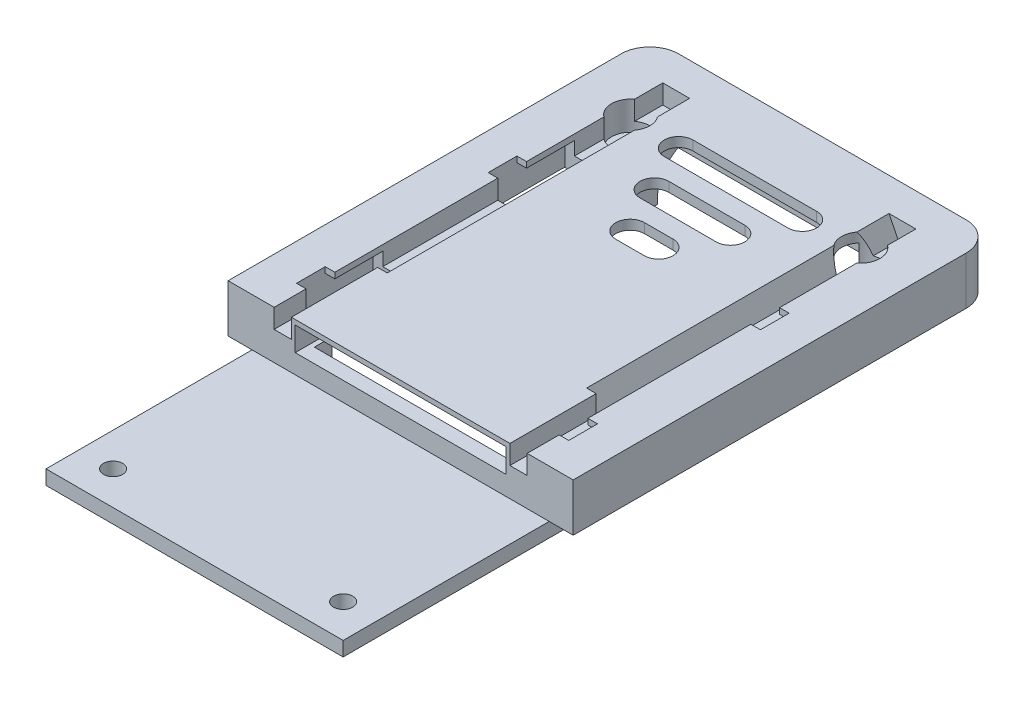
SolidWorks part; units mm, degrees
ref_plane "前视基准面" through (0, 0, 0) normal (0, 0, 1) x (1, 0, 0)
ref_plane "上视基准面" through (0, 0, 0) normal (0, 1, 0) x (1, 0, 0)
ref_plane "右视基准面" through (0, 0, 0) normal (1, 0, 0) x (0, 0, -1)
sketch "草图1" plane through (0, 0, 0) normal (0, 1, 0) x (1, 0, 0)
  line L0 (18, -21) -> (-18, 21) construction
  line L1 (-18, 21) -> (18, 21)
  line L2 (-18, 21) -> (-18, -21)
  line L3 (-18, -21) -> (18, -21)
  line L4 (18, 21) -> (18, -21)
  line L5 (18, 21) -> (-18, -21) construction
  point P4 (0, 0)
  dimension "D1" = 36
  dimension "D2" = 42
extrude "凸台-拉伸1" add sketch "草图1" along normal blind 5
sketch "草图2" plane through (0, 5, 0) normal (0, 1, 0) x (1, 0, 0)
  line L0 (-18, -21) -> (18, -21) construction
  line L1 (-13.2, -21) -> (-11.4, -21)
  line L2 (-13.2, -21) -> (-13.2, 19.55)
  line L3 (-13.2, 19.55) -> (-11.4, 19.55)
  line L4 (-11.4, -21) -> (-11.4, 19.55)
  line L5 (-18, 21) -> (-18, -21) construction
  line L6 (18, 21) -> (-18, 21) construction
  line L7 (0, -21) -> (0, 21) construction
  line L8 (11.4, -21) -> (11.4, 19.55)
  line L9 (13.2, 19.55) -> (11.4, 19.55)
  line L10 (13.2, -21) -> (13.2, 19.55)
  line L11 (13.2, -21) -> (11.4, -21)
  dimension "D1" = 1.8
  dimension "D2" = 4.8
  dimension "D3" = 1.45
extrude "切除-拉伸1" cut sketch "草图2" against normal blind 2
sketch "草图3" plane through (0, 5, 0) normal (0, 1, 0) x (1, 0, 0)
  line L0 (-11.4, -21) -> (11.4, -21) construction
  line L1 (-10.5944, -21) -> (10.4056, -21)
  line L2 (-10.5944, -21) -> (-10.5944, -12.5)
  line L3 (-10.5944, -12.5) -> (10.4056, -12.5)
  line L4 (10.4056, -21) -> (10.4056, -12.5)
  dimension "D1" = 21
  dimension "D2" = 8.5
sketch "草图4" plane through (0, 5, 0) normal (0, 1, 0) x (1, 0, 0)
  line L0 (13.2, -21) -> (13.2, 19.55) construction
  line L1 (13.2, -17.6667) -> (14.2, -17.6667)
  line L2 (13.2, -17.6667) -> (13.2, -14.6667)
  line L3 (13.2, -14.6667) -> (14.2, -14.6667)
  line L4 (14.2, -17.6667) -> (14.2, -14.6667)
  line L5 (13.2, -21) -> (18, -21) construction
  line L6 (13.2, -21) -> (13.2, 19.55) construction
  line L7 (13.2, 2.3333) -> (14.2, 2.3333)
  line L8 (13.2, 2.3333) -> (13.2, 5.3333)
  line L9 (13.2, 5.3333) -> (14.2, 5.3333)
  line L10 (14.2, 2.3333) -> (14.2, 5.3333)
  line L11 (-13.2, 19.55) -> (-13.2, -21) construction
  line L22 (-13.2, -17.6667) -> (-14.2017, -17.6667)
  line L23 (-13.2, -17.6667) -> (-13.2, -14.6667)
  line L24 (-13.2, -14.6667) -> (-14.2017, -14.6667)
  line L25 (-14.2017, -17.6667) -> (-14.2017, -14.6667)
  line L26 (-13.2, 19.55) -> (-13.2, -21) construction
  line L27 (-13.2, 2.3333) -> (-14.2017, 2.3333)
  line L28 (-13.2, 2.3333) -> (-13.2, 5.3333)
  line L29 (-13.2, 5.3333) -> (-14.2017, 5.3333)
  line L30 (-14.2017, 2.3333) -> (-14.2017, 5.3333)
  line L31 (-18, -21) -> (-13.2, -21) construction
  point P26 (-13.7008, 2.3333)
  dimension "D1" = 3
  dimension "D2" = 3.3333
  dimension "D3" = 1
  dimension "D4" = 17
  dimension "D5" = 3
  dimension "D6" = 1
  dimension "D7" = 3
  dimension "D8" = 1.0017
  dimension "D9" = 17
  dimension "D10" = 3
  dimension "D11" = 1.0017
  dimension "D12" = 3.3333
extrude "切除-拉伸2" cut sketch "草图4" against normal through all
sketch "草图5" plane through (0, 0, 0) normal (0, -1, 0) x (1, 0, 0)
  line L1 (-14.2017, 17.6667) -> (-12.4, 17.6667)
  line L2 (-14.2017, 17.6667) -> (-14.2017, 9.6667)
  line L3 (-14.2017, 9.6667) -> (-12.4, 9.6667)
  line L4 (-12.4, 17.6667) -> (-12.4, 9.6667)
  line L5 (-18, -21) -> (-18, 21) construction
  line L6 (18, 21) -> (18, -21) construction
  line L7 (14.2, 17.6667) -> (12.4, 17.6667)
  line L8 (14.2, 17.6667) -> (14.2, 9.6667)
  line L9 (14.2, 9.6667) -> (12.4, 9.6667)
  line L10 (12.4, 17.6667) -> (12.4, 9.6667)
  line L11 (-14.2017, -2.3333) -> (-12.4, -2.3333)
  line L12 (-14.2017, -2.3333) -> (-14.2017, -10.3333)
  line L13 (-14.2017, -10.3333) -> (-12.4, -10.3333)
  line L14 (-12.4, -2.3333) -> (-12.4, -10.3333)
  line L15 (14.2, -2.3333) -> (12.4, -2.3333)
  line L16 (14.2, -2.3333) -> (14.2, -10.3333)
  line L17 (14.2, -10.3333) -> (12.4, -10.3333)
  line L18 (12.4, -2.3333) -> (12.4, -10.3333)
  dimension "D1" = 8
  dimension "D2" = 5.6
  dimension "D3" = 8
  dimension "D4" = 5.6
  dimension "D5" = 5.6
  dimension "D6" = 8
  dimension "D7" = 8
  dimension "D8" = 5.6
extrude "切除-拉伸3" cut sketch "草图5" against normal blind 4.4
ref_plane "基准面5" through (0, 0, 12) normal (0, 0, 1) x (1, 0, 0)
sketch "草图9" plane through (0, 0, 12) normal (0, 0, 1) x (1, 0, 0)
  line L0 (-11.4, 5) -> (-10.4, 5)
  line L1 (-10.5944, 5) -> (10.4056, 5) construction
  line L2 (-10.4, 5) -> (-11.4, 3)
  line L3 (-11.4, 3) -> (-11.4, 5)
  line L4 (11.4, 5) -> (11.4, 3)
  line L5 (11.4, 3) -> (10.4, 5)
  line L6 (10.4, 5) -> (11.4, 5)
  dimension "D1" = 1
  dimension "D2" = 1
extrude "切除-拉伸4" cut sketch "草图9" against normal up to surface (31.55 mm away) up to face at (-12.3, 4, -19.55)
sketch "草图11" plane through (0, 0, 21) normal (0, 0, 1) x (1, 0, 0)
  line L1 (-11, 4.5) -> (11, 4.5)
  line L2 (-11, 4.5) -> (-11, 2)
  line L3 (-11, 2) -> (11, 2)
  line L4 (11, 4.5) -> (11, 2)
  line L5 (0, 2) -> (0, 0) construction
  line L7 (-10.5944, 5) -> (10.4056, 5) construction
  dimension "D1" = 0.5
  dimension "D2" = 2.5
  dimension "D3" = 22
extrude "切除-拉伸5" cut sketch "草图11" against normal blind 8.6
sketch "草图12" plane through (0, 5, 0) normal (0, 1, 0) x (1, 0, 0)
  line L0 (-6.4662, 14.4686) -> (6.4369, 14.4686) construction
  line L1 (-6.4662, 15.9686) -> (6.4369, 15.9686)
  line L2 (-6.4662, 12.9686) -> (6.4369, 12.9686)
  line L3 (-3.9955, 9.4686) -> (3.9437, 9.4686) construction
  line L4 (-3.9955, 10.9686) -> (3.9437, 10.9686)
  line L5 (-3.9955, 7.9686) -> (3.9437, 7.9686)
  line L6 (-1.5248, 4.4686) -> (1.4505, 4.4686) construction
  line L7 (-1.5248, 5.9686) -> (1.4505, 5.9686)
  line L8 (-1.5248, 2.9686) -> (1.4505, 2.9686)
  line L9 (0, 21) -> (-0.0944, -21) construction
  line L10 (18, 21) -> (-18, 21) construction
  line L11 (-10.5944, -21) -> (10.4056, -21) construction
  line L12 (-1.5248, 4.4686) -> (-6.4662, 14.4686) construction
  arc A0 (-6.4662, 15.9686) -> (-6.4662, 12.9686) centre (-6.4662, 14.4686) ccw
  arc A1 (6.4369, 12.9686) -> (6.4369, 15.9686) centre (6.4369, 14.4686) ccw
  arc A2 (-3.9955, 10.9686) -> (-3.9955, 7.9686) centre (-3.9955, 9.4686) ccw
  arc A3 (3.9437, 7.9686) -> (3.9437, 10.9686) centre (3.9437, 9.4686) ccw
  arc A4 (-1.5248, 5.9686) -> (-1.5248, 2.9686) centre (-1.5248, 4.4686) ccw
  arc A5 (1.4505, 2.9686) -> (1.4505, 5.9686) centre (1.4505, 4.4686) ccw
  point P2 (-0.0147, 14.4686)
  point P9 (-0.0259, 9.4686)
  point P16 (-0.0371, 4.4686)
  dimension "D1" = 2
  dimension "D2" = 2
  dimension "D3" = 3
  dimension "D4" = 3
  dimension "D5" = 3
extrude "切除-拉伸6" cut sketch "草图12" against normal up to surface (5 mm away) up to face at (13.3, 0, -6.3333)
sketch "草图13" plane through (0, 0, 0) normal (0, -1, 0) x (1, 0, 0)
  line L5 (-10.5944, 21) -> (10.4056, 21) construction
  line L6 (-16.5, -19.5) -> (16.5, -19.5)
  line L8 (-16.5, -19.5) -> (-16.5, 19.5)
  line L9 (-16.5, 19.5) -> (16.5, 19.5)
  line L10 (16.5, -19.5) -> (16.5, 19.5)
  line L11 (18, 21) -> (18, -21) construction
  line L12 (-18, -21) -> (-18, 21) construction
  line L13 (18, -21) -> (-18, -21) construction
  point P0 (0, 0)
  dimension "D1" = 1.5
  dimension "D2" = 1.5
  dimension "D3" = 1.5
  dimension "D4" = 1.5
extrude "切除-拉伸7" cut sketch "草图13" against normal blind 1.5
sketch "草图14" plane through (0, 1.5, 0) normal (0, -1, 0) x (1, 0, 0)
  line L0 (-16.5, -19.5) -> (16.5, -19.5) construction
  line L1 (-10.5, -19.5) -> (10.5, -19.5)
  line L2 (-10.5, -19.5) -> (-10.5, 19.5)
  line L3 (-10.5, 19.5) -> (10.5, 19.5)
  line L4 (10.5, -19.5) -> (10.5, 19.5)
  line L5 (16.5, 19.5) -> (-16.5, 19.5) construction
  line L8 (0, 19.5) -> (0, -19.5) construction
  dimension "D2" = 21
extrude "切除-拉伸8" cut sketch "草图14" against normal blind 2.5
sketch "草图15" plane through (0, 0, 0) normal (0, -1, 0) x (1, 0, 0)
  line L7 (-10.5, 17.6667) -> (-10.5, 19.5)
  line L8 (18, -21) -> (-18, -21) construction
  line L9 (-15.5, 17.6667) -> (15.5, 17.6667)
  line L10 (-15.5, 17.6667) -> (-15.5, 42.5)
  line L11 (-15.5, 42.5) -> (15.5, 42.5)
  line L12 (15.5, 17.6667) -> (15.5, 42.5)
  line L13 (16.5, 19.5) -> (-16.5, 19.5) construction
  line L14 (-10.5, 19.5) -> (10.5, 19.5)
  line L15 (10.5, 19.5) -> (10.5, 17.6667)
  line L16 (10.5, -19.5) -> (10.5, 19.5) construction
  line L17 (-10.5, 19.5) -> (-10.5, -19.5) construction
  line L19 (0, 42.5) -> (0, 0) construction
  line L21 (-12.4, 17.6667) -> (-14.2017, 17.6667) construction
  line M11 (-16.5, 19.5) -> (16.5, 19.5)
  line M28 (18, 21) -> (-18, 21)
  dimension "D1" = 63.5
  dimension "D2" = 31
extrude "凸台-拉伸2" add sketch "草图15" along normal blind 1.5 separate body contours L19 L11 L10 M28 | L11 L19 L12 M28 | L19 L14 L12 M28 M11 | L19 L10 M28 M11 | L10 L9 L7 M11 | L15 L9 L12 M11 region at (-13, 0, 18.5834) region at (-7.75, 0, 20.25) region at (7.75, 0, 20.25) region at (13, 0, 18.5834) region at (-7.75, 0, 31.75) region at (7.75, 0, 31.75)
sketch "草图16" plane through (0, 1.5, 0) normal (0, -1, 0) x (1, 0, 0)
  line L0 (10.5, 19.5) -> (10.5, 17.6667) construction
  line L1 (-16.5, 17.6667) -> (-10.5, 17.6667)
  line L2 (-16.5, 17.6667) -> (-16.5, 19.5)
  line L3 (-16.5, 19.5) -> (-10.5, 19.5)
  line L4 (-10.5, 17.6667) -> (-10.5, 19.5)
  line L5 (10.5, 17.6667) -> (16.5, 17.6667)
  line L6 (10.5, 17.6667) -> (10.5, 19.5)
  line L7 (10.5, 19.5) -> (16.5, 19.5)
  line L8 (16.5, 17.6667) -> (16.5, 19.5)
  line L9 (-16.5, 19.5) -> (-16.5, -19.5) construction
  line L10 (-10.5, 17.6667) -> (-10.5, 19.5) construction
  line L11 (16.5, -19.5) -> (16.5, 19.5) construction
  line L12 (-12.4, 17.6667) -> (-13.2, 17.6667) construction
  line M2 (-10.5, -19.5) -> (-10.5, 19.5)
  line M3 (-10.5, 19.5) -> (-16.5, 19.5)
  line M5 (-14.2017, 17.6667) -> (-12.4, 17.6667)
  line M12 (-16.5, 19.5) -> (-16.5, -19.5)
extrude "凸台-拉伸3" add sketch "草图16" along normal up to surface (1.5 mm away) contours L5 L8 L7 L6 | L1 M12 M5 M2 M3 region at (-13.5, 1.5, 18.5834) region at (13.5, 1.5, 18.5834) up to face at (0, 0, 24.3334)
sketch "草图17" plane through (0, -1.5, 0) normal (0, -1, 0) x (1, 0, 0)
  line L6 (0, 42) -> (0, -18) construction
  line L7 (15, 42) -> (-15, 42)
  line L8 (15, 42) -> (15, -18)
  line L13 (15, -18) -> (-15, -18)
  line L14 (-15, 42) -> (-15, -18)
  line L19 (15, 12) -> (-15, 12) construction
  line L20 (18, 21) -> (18, -21) construction
  line L23 (18, -21) -> (-18, -21) construction
  circle A4 centre (12, 39) radius 1
  circle A8 centre (-12, 39) radius 1
  circle A9 centre (-12, -15) radius 1
  circle A10 centre (12, -15) radius 1
  dimension "D6" = 3
  dimension "D4" = 3
  dimension "D5" = 2
  dimension "D7" = 6
  dimension "D1" = 30
  dimension "D2" = 60
  dimension "D3" = 3
extrude "切除-拉伸9" cut sketch "草图17" against normal blind 10 contours A10 | A9 | A8 | A4 region at (12, -1.5, 39) region at (-12, -1.5, 39) region at (-12, -1.5, -15) region at (12, -1.5, -15)
sketch "草图18" plane through (0, 5, 0) normal (0, 1, 0) x (1, 0, 0)
  line L0 (0, 21) -> (0, 0) construction
  line L1 (18, 21) -> (-18, 21) construction
  circle A2 centre (-12, 15) radius 2
  circle A3 centre (12, 15) radius 2
  dimension "D1" = 4
  dimension "D2" = 4
extrude "切除-拉伸10" cut sketch "草图18" against normal blind 3
sketch "草图20" plane through (0, 0, -21) normal (0, 0, -1) x (-1, 0, 0)
  line L1 (-18, 0) -> (18, 0)
  line L2 (-18, 0) -> (-18, 5)
  line L3 (-18, 5) -> (18, 5)
  line L4 (18, 0) -> (18, 5)
extrude "凸台-拉伸4" add sketch "草图20" along normal blind 2
fillet "圆角1" radius 3 2 edges at (-18, 2.5, -23) (18, 2.5, -23)
sketch "草图22" plane through (0, 1.5, 0) normal (0, -1, 0) x (-1, 0, 0)
  line L0 (-10.5, 16.3229) -> (-10.5, 13.6771)
  line L1 (10.5, 13.6771) -> (10.5, 16.3229)
  circle A0 centre (12, 15) radius 2
  circle A1 centre (-12, 15) radius 2
  circle A3 centre (-12, 15) radius 1
  circle M3 centre (12, 15) radius 1
  line M11 (10.5, 19.5) -> (10.5, -17.6667)
extrude "凸台-拉伸5" add sketch "草图22" along normal blind 4.5 contours L0 A1 | A0 M11 M3 region at (10.5532, 1.5, -15) region at (-10.5532, 1.5, -15)
fillet "圆角2" radius 3.5 2 edges at (14, 1.5, -15) (-14, 1.5, -15)
sketch "草图23" plane through (0, -1.5, 0) normal (0, -1, 0) x (1, 0, 0)
  circle A0 centre (-12, 39) radius 2
  circle A1 centre (12, 39) radius 2
  circle A2 centre (-12, 39) radius 1
  circle A3 centre (12, 39) radius 1
  dimension "D1" = 4
  dimension "D2" = 4
extrude "凸台-拉伸6" add sketch "草图23" along normal blind 1.5
fillet "圆角3" radius 1 2 edges at (-12, -1.5, 37) (12, -1.5, 37)
